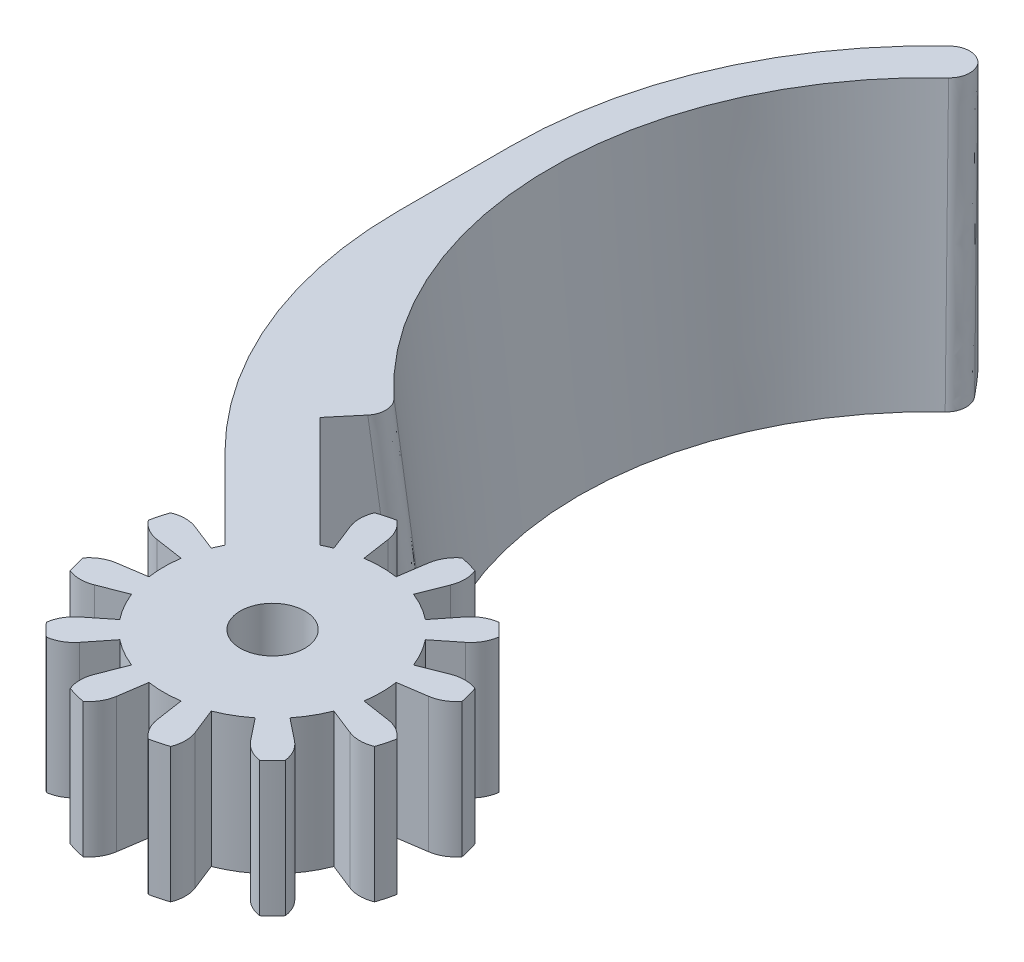
SolidWorks part; units mm, degrees
ref_plane "Plan de face" through (0, 0, 0) normal (0, 0, 1) x (1, 0, 0)
ref_plane "Plan de dessus" through (0, 0, 0) normal (0, 1, 0) x (1, 0, 0)
ref_plane "Plan de droite" through (0, 0, 0) normal (1, 0, 0) x (0, 0, -1)
sketch "Esquisse1" plane through (0, 0, 0) normal (0, 1, 0) x (1, 0, 0)
  line L0 (0, 0) -> (0, 27.3284) construction
  line L1 (-38.1202, 0) -> (19.7056, 0) construction
  line L2 (8.75, 40) -> (-53.1888, 40) construction
  line L3 (8.75, 40) -> (-13.9541, 12.9423) construction
  line L4 (8.75, 40) -> (-15.7208, 69.1632) construction
  line L5 (-22.25, 47.3971) -> (-22.25, -30.6529) construction
  line L6 (0, 0) -> (-33.9162, 33.9162) construction
  line L7 (-13.1703, 9.6348) -> (-7.1971, 3.6616)
  line L8 (-11.8794, 15.4149) -> (-3.6616, 7.1971)
  line L9 (-22.25, 40) -> (-22.25, 31.5551)
  line L10 (0, 0) -> (3.5575, 13.2769) construction
  line L11 (0, 0) -> (7.0447, 12.2018) construction
  line L12 (0, 0) -> (4.3209, 13.1034) construction
  line L13 (0, 0) -> (5.1162, 12.9881) construction
  line L14 (3.7383, 9.4903) -> (2.9595, 7.5131)
  line L15 (1.5077, 10.088) -> (1.1936, 7.9863)
  line L16 (6.3496, 7.9826) -> (5.0268, 6.3196)
  line L17 (7.9826, 6.3496) -> (6.3196, 5.0268)
  line L18 (9.4903, 3.7383) -> (7.5131, 2.9595)
  line L19 (10.088, 1.5077) -> (7.9863, 1.1936)
  line L20 (10.088, -1.5077) -> (7.9863, -1.1936)
  line L21 (9.4903, -3.7383) -> (7.5131, -2.9595)
  line L22 (7.9826, -6.3496) -> (6.3196, -5.0268)
  line L23 (6.3496, -7.9826) -> (5.0268, -6.3196)
  line L24 (3.7383, -9.4903) -> (2.9595, -7.5131)
  line L25 (1.5077, -10.088) -> (1.1936, -7.9863)
  line L26 (-1.5077, -10.088) -> (-1.1936, -7.9863)
  line L27 (-3.7383, -9.4903) -> (-2.9595, -7.5131)
  line L28 (-6.3496, -7.9826) -> (-5.0268, -6.3196)
  line L29 (-7.9826, -6.3496) -> (-6.3196, -5.0268)
  line L30 (-9.4903, -3.7383) -> (-7.5131, -2.9595)
  line L31 (-10.088, -1.5077) -> (-7.9863, -1.1936)
  line L32 (-10.088, 1.5077) -> (-7.9863, 1.1936)
  line L33 (-9.4903, 3.7383) -> (-7.5131, 2.9595)
  line L34 (-17.25, 40) -> (-17.25, -30.6529) construction
  line L36 (-3.7383, 9.4903) -> (-2.9595, 7.5131)
  line L37 (-1.5077, 10.088) -> (-1.1936, 7.9863)
  line L38 (-7.9826, 6.3496) -> (-6.3196, 5.0268) [skipped]
  line L39 (-6.3496, 7.9826) -> (-5.0268, 6.3196) [skipped]
  line L40 (-11.8794, 15.4149) -> (-7.9625, 20.0828)
  line L41 (-10.1877, 62.5691) -> (-7.9625, 59.9172)
  line L42 (8.75, 40) -> (8.75, 0) construction
  circle A0 centre (0, 0) radius 11.9 construction
  circle A1 centre (0, 0) radius 10.2 construction
  circle A2 centre (0, 0) radius 8.075 construction
  circle A3 centre (8.75, 40) radius 25 construction
  arc A4 (-7.9625, 59.9172) -> (-7.9625, 20.0828) centre (8.75, 40) ccw
  arc A5 (-22.25, 40) -> (-12.3581, 62.7035) centre (8.75, 40) cw
  arc A7 (3.7266, 11.3014) -> (3.7383, 9.4903) centre (1.4762, 10.3813) cw
  arc A8 (3.7266, 11.3014) -> (2.4233, 11.6506) centre (0, 0) ccw
  arc A9 (4.0375, 6.9932) -> (2.9595, 7.5131) centre (0, 0) ccw
  arc A10 (0, 8.075) -> (1.1936, 7.9863) centre (0, 0) cw
  arc A11 (2.4233, 11.6506) -> (1.5077, 10.088) centre (3.9122, 9.7286) ccw
  arc A12 (4.0375, 6.9932) -> (5.0268, 6.3196) centre (0, 0) cw
  arc A13 (7.924, 8.8781) -> (6.3496, 7.9826) centre (8.2524, 6.4691) ccw
  arc A14 (8.8781, 7.924) -> (7.924, 8.8781) centre (0, 0) ccw
  arc A15 (8.8781, 7.924) -> (7.9826, 6.3496) centre (6.4691, 8.2524) cw
  arc A16 (6.9932, 4.0375) -> (6.3196, 5.0268) centre (0, 0) ccw
  arc A17 (6.9932, 4.0375) -> (7.5131, 2.9595) centre (0, 0) cw
  arc A18 (11.3014, 3.7266) -> (9.4903, 3.7383) centre (10.3813, 1.4762) ccw
  arc A19 (11.6506, 2.4233) -> (11.3014, 3.7266) centre (0, 0) ccw
  arc A20 (11.6506, 2.4233) -> (10.088, 1.5077) centre (9.7286, 3.9122) cw
  arc A21 (8.075, 0) -> (7.9863, 1.1936) centre (0, 0) ccw
  arc A22 (8.075, 0) -> (7.9863, -1.1936) centre (0, 0) cw
  arc A23 (11.6506, -2.4233) -> (10.088, -1.5077) centre (9.7286, -3.9122) ccw
  arc A24 (11.3014, -3.7266) -> (11.6506, -2.4233) centre (0, 0) ccw
  arc A25 (11.3014, -3.7266) -> (9.4903, -3.7383) centre (10.3813, -1.4762) cw
  arc A26 (6.9932, -4.0375) -> (7.5131, -2.9595) centre (0, 0) ccw
  arc A27 (6.9932, -4.0375) -> (6.3196, -5.0268) centre (0, 0) cw
  arc A28 (8.8781, -7.924) -> (7.9826, -6.3496) centre (6.4691, -8.2524) ccw
  arc A29 (7.924, -8.8781) -> (8.8781, -7.924) centre (0, 0) ccw
  arc A30 (7.924, -8.8781) -> (6.3496, -7.9826) centre (8.2524, -6.4691) cw
  arc A31 (4.0375, -6.9932) -> (5.0268, -6.3196) centre (0, 0) ccw
  arc A32 (4.0375, -6.9932) -> (2.9595, -7.5131) centre (0, 0) cw
  arc A33 (3.7266, -11.3014) -> (3.7383, -9.4903) centre (1.4762, -10.3813) ccw
  arc A34 (2.4233, -11.6506) -> (3.7266, -11.3014) centre (0, 0) ccw
  arc A35 (2.4233, -11.6506) -> (1.5077, -10.088) centre (3.9122, -9.7286) cw
  arc A36 (0, -8.075) -> (1.1936, -7.9863) centre (0, 0) ccw
  arc A37 (0, -8.075) -> (-1.1936, -7.9863) centre (0, 0) cw
  arc A38 (-2.4233, -11.6506) -> (-1.5077, -10.088) centre (-3.9122, -9.7286) ccw
  arc A39 (-3.7266, -11.3014) -> (-2.4233, -11.6506) centre (0, 0) ccw
  arc A40 (-3.7266, -11.3014) -> (-3.7383, -9.4903) centre (-1.4762, -10.3813) cw
  arc A41 (-4.0375, -6.9932) -> (-2.9595, -7.5131) centre (0, 0) ccw
  arc A42 (-4.0375, -6.9932) -> (-5.0268, -6.3196) centre (0, 0) cw
  arc A43 (-7.924, -8.8781) -> (-6.3496, -7.9826) centre (-8.2524, -6.4691) ccw
  arc A44 (-8.8781, -7.924) -> (-7.924, -8.8781) centre (0, 0) ccw
  arc A45 (-8.8781, -7.924) -> (-7.9826, -6.3496) centre (-6.4691, -8.2524) cw
  arc A46 (-6.9932, -4.0375) -> (-6.3196, -5.0268) centre (0, 0) ccw
  arc A47 (-6.9932, -4.0375) -> (-7.5131, -2.9595) centre (0, 0) cw
  arc A48 (-11.3014, -3.7266) -> (-9.4903, -3.7383) centre (-10.3813, -1.4762) ccw
  arc A49 (-11.6506, -2.4233) -> (-11.3014, -3.7266) centre (0, 0) ccw
  arc A50 (-11.6506, -2.4233) -> (-10.088, -1.5077) centre (-9.7286, -3.9122) cw
  arc A51 (-8.075, 0) -> (-7.9863, -1.1936) centre (0, 0) ccw
  arc A52 (-8.075, 0) -> (-7.9863, 1.1936) centre (0, 0) cw
  arc A53 (-11.6506, 2.4233) -> (-10.088, 1.5077) centre (-9.7286, 3.9122) ccw
  arc A54 (-11.3014, 3.7266) -> (-11.6506, 2.4233) centre (0, 0) ccw
  arc A55 (-11.3014, 3.7266) -> (-9.4903, 3.7383) centre (-10.3813, 1.4762) cw
  arc A56 (-2.9595, 7.5131) -> (-3.6616, 7.1971) centre (0, 0) ccw
  arc A57 (-7.5131, 2.9595) -> (-7.1971, 3.6616) centre (0, 0) cw
  arc A60 (-13.1703, 9.6348) -> (-22.25, 31.5551) centre (8.75, 31.5551) cw
  arc A61 (-12.3581, 62.7035) -> (-10.1877, 62.5691) centre (-11.3368, 61.6049) cw
  arc A63 (-3.7266, 11.3014) -> (-3.7383, 9.4903) centre (-1.4762, 10.3813) ccw
  arc A64 (-2.4233, 11.6506) -> (-3.7266, 11.3014) centre (0, 0) ccw
  arc A65 (-2.4233, 11.6506) -> (-1.5077, 10.088) centre (-3.9122, 9.7286) cw
  arc A66 (0, 8.075) -> (-1.1936, 7.9863) centre (0, 0) ccw
  arc A67 (-8.8781, 7.924) -> (-7.9826, 6.3496) centre (-6.4691, 8.2524) ccw [skipped]
  arc A68 (-7.924, 8.8781) -> (-8.8781, 7.924) centre (0, 0) ccw [skipped]
  arc A69 (-7.924, 8.8781) -> (-6.3496, 7.9826) centre (-8.2524, 6.4691) cw [skipped]
  arc A70 (-6.9932, 4.0375) -> (-6.3196, 5.0268) centre (0, 0) cw [skipped]
  arc A71 (-4.0375, 6.9932) -> (-5.0268, 6.3196) centre (0, 0) ccw [skipped]
  arc A72 (-4.0375, 6.9932) -> (-2.9595, 7.5131) centre (0, 0) cw [skipped]
  arc A73 (-6.9932, 4.0375) -> (-7.5131, 2.9595) centre (0, 0) ccw [skipped]
  point P72 (0, 0)
  point P135 (-17.25, 20.2855)
  point P138 (-22.25, 18.7145)
  point P155 (-11.1764, 63.7474)
  point P169 (-10.855, 16.6356)
  point P176 (-17.25, 23.2668)
  dimension "D1" = 50
  dimension "D2" = 50
  dimension "D5" = 20.4
  dimension "D6" = 23.8
  dimension "D7" = 16.15
  dimension "D11" = 26
  dimension "D12" = 5
  dimension "D17" = 12
  dimension "D18" = 5
  dimension "D20" = 1.5
  dimension "D3" = 40
  dimension "D4" = 50
  dimension "D9" = 45
  dimension "D10" = 5
  dimension "D13" = 8.75
  dimension "D14" = 3.25
  dimension "D15" = 6.5
  dimension "D16" = 15
extrude "Boss.-Extru.1" add sketch "Esquisse1" along normal blind 10
sketch "Esquisse2" plane through (0, 0, 0) normal (0, -1, 0) x (1, 0, 0)
  line L0 (-11.8794, -15.4149) -> (-7.9625, -20.0828) construction
  line L30 (-2.9595, -7.5131) -> (-3.7383, -9.4903)
  line L31 (-1.5077, -10.088) -> (-1.1936, -7.9863)
  line L32 (1.1936, -7.9863) -> (1.5077, -10.088)
  line L33 (3.7383, -9.4903) -> (2.9595, -7.5131)
  line L34 (5.0268, -6.3196) -> (6.3496, -7.9826)
  line L35 (7.9826, -6.3496) -> (6.3196, -5.0268)
  line L36 (7.5131, -2.9595) -> (9.4903, -3.7383)
  line L37 (10.088, -1.5077) -> (7.9863, -1.1936)
  line L38 (7.9863, 1.1936) -> (10.088, 1.5077)
  line L39 (9.4903, 3.7383) -> (7.5131, 2.9595)
  line L40 (6.3196, 5.0268) -> (7.9826, 6.3496)
  line L41 (6.3496, 7.9826) -> (5.0268, 6.3196)
  line L42 (2.9595, 7.5131) -> (3.7383, 9.4903)
  line L43 (1.5077, 10.088) -> (1.1936, 7.9863)
  line L44 (-1.1936, 7.9863) -> (-1.5077, 10.088)
  line L45 (-3.7383, 9.4903) -> (-2.9595, 7.5131)
  line L46 (-5.0268, 6.3196) -> (-6.3496, 7.9826)
  line L47 (-7.9826, 6.3496) -> (-6.3196, 5.0268)
  line L48 (-7.5131, 2.9595) -> (-9.4903, 3.7383)
  line L49 (-10.088, 1.5077) -> (-7.9863, 1.1936)
  line L50 (-7.9863, -1.1936) -> (-10.088, -1.5077)
  line L51 (-9.4903, -3.7383) -> (-7.5131, -2.9595)
  line L52 (-7.1971, -3.6616) -> (-13.1703, -9.6348)
  line L54 (-11.8794, -15.4149) -> (-3.6616, -7.1971)
  line L55 (-11.8794, -15.4149) -> (-3.6616, -7.1971)
  line L58 (-2.9595, -7.5131) -> (-3.7383, -9.4903)
  line L59 (-1.5077, -10.088) -> (-1.1936, -7.9863)
  line L60 (1.1936, -7.9863) -> (1.5077, -10.088)
  line L61 (3.7383, -9.4903) -> (2.9595, -7.5131)
  line L62 (5.0268, -6.3196) -> (6.3496, -7.9826)
  line L63 (7.9826, -6.3496) -> (6.3196, -5.0268)
  line L64 (7.5131, -2.9595) -> (9.4903, -3.7383)
  line L65 (10.088, -1.5077) -> (7.9863, -1.1936)
  line L66 (7.9863, 1.1936) -> (10.088, 1.5077)
  line L67 (9.4903, 3.7383) -> (7.5131, 2.9595)
  line L68 (6.3196, 5.0268) -> (7.9826, 6.3496)
  line L69 (6.3496, 7.9826) -> (5.0268, 6.3196)
  line L70 (2.9595, 7.5131) -> (3.7383, 9.4903)
  line L71 (1.5077, 10.088) -> (1.1936, 7.9863)
  line L72 (-1.1936, 7.9863) -> (-1.5077, 10.088)
  line L73 (-3.7383, 9.4903) -> (-2.9595, 7.5131)
  line L74 (-5.0268, 6.3196) -> (-6.3496, 7.9826)
  line L75 (-7.9826, 6.3496) -> (-6.3196, 5.0268)
  line L76 (-7.5131, 2.9595) -> (-9.4903, 3.7383)
  line L77 (-10.088, 1.5077) -> (-7.9863, 1.1936)
  line L78 (-7.9863, -1.1936) -> (-10.088, -1.5077)
  line L79 (-9.4903, -3.7383) -> (-7.5131, -2.9595)
  line L80 (-7.1971, -3.6616) -> (-13.1703, -9.6348)
  line L84 (-22.25, -31.5551) -> (-22.25, -40)
  line L85 (-22.25, -31.5551) -> (-22.25, -40)
  line L86 (-10.1877, -62.5691) -> (-7.9625, -59.9172)
  line L87 (-10.1877, -62.5691) -> (-7.9625, -59.9172)
  line L88 (-7.9625, -20.0828) -> (-11.8794, -15.4149)
  line L89 (-7.9625, -20.0828) -> (-11.8794, -15.4149)
  arc A0 (-11.1764, -16.2526) -> (-15.2252, -59.6518) centre (8.75, -40) ccw
  arc A56 (-3.7383, -9.4903) -> (-3.7266, -11.3014) centre (-1.4762, -10.3813) ccw
  arc A57 (-3.7266, -11.3014) -> (-2.4233, -11.6506) centre (0, 0) ccw
  arc A58 (-2.4233, -11.6506) -> (-1.5077, -10.088) centre (-3.9122, -9.7286) ccw
  arc A59 (-1.1936, -7.9863) -> (1.1936, -7.9863) centre (0, 0) ccw
  arc A60 (1.5077, -10.088) -> (2.4233, -11.6506) centre (3.9122, -9.7286) ccw
  arc A61 (2.4233, -11.6506) -> (3.7266, -11.3014) centre (0, 0) ccw
  arc A62 (3.7266, -11.3014) -> (3.7383, -9.4903) centre (1.4762, -10.3813) ccw
  arc A63 (2.9595, -7.5131) -> (5.0268, -6.3196) centre (0, 0) ccw
  arc A64 (6.3496, -7.9826) -> (7.924, -8.8781) centre (8.2524, -6.4691) ccw
  arc A65 (7.924, -8.8781) -> (8.8781, -7.924) centre (0, 0) ccw
  arc A66 (8.8781, -7.924) -> (7.9826, -6.3496) centre (6.4691, -8.2524) ccw
  arc A67 (6.3196, -5.0268) -> (7.5131, -2.9595) centre (0, 0) ccw
  arc A68 (9.4903, -3.7383) -> (11.3014, -3.7266) centre (10.3813, -1.4762) ccw
  arc A69 (11.3014, -3.7266) -> (11.6506, -2.4233) centre (0, 0) ccw
  arc A70 (11.6506, -2.4233) -> (10.088, -1.5077) centre (9.7286, -3.9122) ccw
  arc A71 (7.9863, -1.1936) -> (7.9863, 1.1936) centre (0, 0) ccw
  arc A72 (10.088, 1.5077) -> (11.6506, 2.4233) centre (9.7286, 3.9122) ccw
  arc A73 (11.6506, 2.4233) -> (11.3014, 3.7266) centre (0, 0) ccw
  arc A74 (11.3014, 3.7266) -> (9.4903, 3.7383) centre (10.3813, 1.4762) ccw
  arc A75 (7.5131, 2.9595) -> (6.3196, 5.0268) centre (0, 0) ccw
  arc A76 (7.9826, 6.3496) -> (8.8781, 7.924) centre (6.4691, 8.2524) ccw
  arc A77 (8.8781, 7.924) -> (7.924, 8.8781) centre (0, 0) ccw
  arc A78 (7.924, 8.8781) -> (6.3496, 7.9826) centre (8.2524, 6.4691) ccw
  arc A79 (5.0268, 6.3196) -> (2.9595, 7.5131) centre (0, 0) ccw
  arc A80 (3.7383, 9.4903) -> (3.7266, 11.3014) centre (1.4762, 10.3813) ccw
  arc A81 (3.7266, 11.3014) -> (2.4233, 11.6506) centre (0, 0) ccw
  arc A82 (2.4233, 11.6506) -> (1.5077, 10.088) centre (3.9122, 9.7286) ccw
  arc A83 (1.1936, 7.9863) -> (-1.1936, 7.9863) centre (0, 0) ccw
  arc A84 (-1.5077, 10.088) -> (-2.4233, 11.6506) centre (-3.9122, 9.7286) ccw
  arc A85 (-2.4233, 11.6506) -> (-3.7266, 11.3014) centre (0, 0) ccw
  arc A86 (-3.7266, 11.3014) -> (-3.7383, 9.4903) centre (-1.4762, 10.3813) ccw
  arc A87 (-2.9595, 7.5131) -> (-5.0268, 6.3196) centre (0, 0) ccw
  arc A88 (-6.3496, 7.9826) -> (-7.924, 8.8781) centre (-8.2524, 6.4691) ccw
  arc A89 (-7.924, 8.8781) -> (-8.8781, 7.924) centre (0, 0) ccw
  arc A90 (-8.8781, 7.924) -> (-7.9826, 6.3496) centre (-6.4691, 8.2524) ccw
  arc A91 (-6.3196, 5.0268) -> (-7.5131, 2.9595) centre (0, 0) ccw
  arc A92 (-9.4903, 3.7383) -> (-11.3014, 3.7266) centre (-10.3813, 1.4762) ccw
  arc A93 (-11.3014, 3.7266) -> (-11.6506, 2.4233) centre (0, 0) ccw
  arc A94 (-11.6506, 2.4233) -> (-10.088, 1.5077) centre (-9.7286, 3.9122) ccw
  arc A95 (-7.9863, 1.1936) -> (-7.9863, -1.1936) centre (0, 0) ccw
  arc A96 (-10.088, -1.5077) -> (-11.6506, -2.4233) centre (-9.7286, -3.9122) ccw
  arc A97 (-11.6506, -2.4233) -> (-11.3014, -3.7266) centre (0, 0) ccw
  arc A98 (-11.3014, -3.7266) -> (-9.4903, -3.7383) centre (-10.3813, -1.4762) ccw
  arc A99 (-7.5131, -2.9595) -> (-7.1971, -3.6616) centre (0, 0) ccw
  arc A102 (-3.6616, -7.1971) -> (-2.9595, -7.5131) centre (0, 0) ccw
  arc A103 (-3.6616, -7.1971) -> (-2.9595, -7.5131) centre (0, 0) ccw
  arc A104 (-13.1703, -9.6348) -> (-22.25, -31.5551) centre (8.75, -31.5551) ccw
  arc A105 (-13.1703, -9.6348) -> (-22.25, -31.5551) centre (8.75, -31.5551) ccw
  arc A109 (-3.7383, -9.4903) -> (-3.7266, -11.3014) centre (-1.4762, -10.3813) ccw
  arc A110 (-3.7266, -11.3014) -> (-2.4233, -11.6506) centre (0, 0) ccw
  arc A111 (-2.4233, -11.6506) -> (-1.5077, -10.088) centre (-3.9122, -9.7286) ccw
  arc A112 (-1.1936, -7.9863) -> (1.1936, -7.9863) centre (0, 0) ccw
  arc A113 (1.5077, -10.088) -> (2.4233, -11.6506) centre (3.9122, -9.7286) ccw
  arc A114 (2.4233, -11.6506) -> (3.7266, -11.3014) centre (0, 0) ccw
  arc A115 (3.7266, -11.3014) -> (3.7383, -9.4903) centre (1.4762, -10.3813) ccw
  arc A116 (2.9595, -7.5131) -> (5.0268, -6.3196) centre (0, 0) ccw
  arc A117 (6.3496, -7.9826) -> (7.924, -8.8781) centre (8.2524, -6.4691) ccw
  arc A118 (7.924, -8.8781) -> (8.8781, -7.924) centre (0, 0) ccw
  arc A119 (8.8781, -7.924) -> (7.9826, -6.3496) centre (6.4691, -8.2524) ccw
  arc A120 (6.3196, -5.0268) -> (7.5131, -2.9595) centre (0, 0) ccw
  arc A121 (9.4903, -3.7383) -> (11.3014, -3.7266) centre (10.3813, -1.4762) ccw
  arc A122 (11.3014, -3.7266) -> (11.6506, -2.4233) centre (0, 0) ccw
  arc A123 (11.6506, -2.4233) -> (10.088, -1.5077) centre (9.7286, -3.9122) ccw
  arc A124 (7.9863, -1.1936) -> (7.9863, 1.1936) centre (0, 0) ccw
  arc A125 (10.088, 1.5077) -> (11.6506, 2.4233) centre (9.7286, 3.9122) ccw
  arc A126 (11.6506, 2.4233) -> (11.3014, 3.7266) centre (0, 0) ccw
  arc A127 (11.3014, 3.7266) -> (9.4903, 3.7383) centre (10.3813, 1.4762) ccw
  arc A128 (7.5131, 2.9595) -> (6.3196, 5.0268) centre (0, 0) ccw
  arc A129 (7.9826, 6.3496) -> (8.8781, 7.924) centre (6.4691, 8.2524) ccw
  arc A130 (8.8781, 7.924) -> (7.924, 8.8781) centre (0, 0) ccw
  arc A131 (7.924, 8.8781) -> (6.3496, 7.9826) centre (8.2524, 6.4691) ccw
  arc A132 (5.0268, 6.3196) -> (2.9595, 7.5131) centre (0, 0) ccw
  arc A133 (3.7383, 9.4903) -> (3.7266, 11.3014) centre (1.4762, 10.3813) ccw
  arc A134 (3.7266, 11.3014) -> (2.4233, 11.6506) centre (0, 0) ccw
  arc A135 (2.4233, 11.6506) -> (1.5077, 10.088) centre (3.9122, 9.7286) ccw
  arc A136 (1.1936, 7.9863) -> (-1.1936, 7.9863) centre (0, 0) ccw
  arc A137 (-1.5077, 10.088) -> (-2.4233, 11.6506) centre (-3.9122, 9.7286) ccw
  arc A138 (-2.4233, 11.6506) -> (-3.7266, 11.3014) centre (0, 0) ccw
  arc A139 (-3.7266, 11.3014) -> (-3.7383, 9.4903) centre (-1.4762, 10.3813) ccw
  arc A140 (-2.9595, 7.5131) -> (-5.0268, 6.3196) centre (0, 0) ccw
  arc A141 (-6.3496, 7.9826) -> (-7.924, 8.8781) centre (-8.2524, 6.4691) ccw
  arc A142 (-7.924, 8.8781) -> (-8.8781, 7.924) centre (0, 0) ccw
  arc A143 (-8.8781, 7.924) -> (-7.9826, 6.3496) centre (-6.4691, 8.2524) ccw
  arc A144 (-6.3196, 5.0268) -> (-7.5131, 2.9595) centre (0, 0) ccw
  arc A145 (-9.4903, 3.7383) -> (-11.3014, 3.7266) centre (-10.3813, 1.4762) ccw
  arc A146 (-11.3014, 3.7266) -> (-11.6506, 2.4233) centre (0, 0) ccw
  arc A147 (-11.6506, 2.4233) -> (-10.088, 1.5077) centre (-9.7286, 3.9122) ccw
  arc A148 (-7.9863, 1.1936) -> (-7.9863, -1.1936) centre (0, 0) ccw
  arc A149 (-10.088, -1.5077) -> (-11.6506, -2.4233) centre (-9.7286, -3.9122) ccw
  arc A150 (-11.6506, -2.4233) -> (-11.3014, -3.7266) centre (0, 0) ccw
  arc A151 (-11.3014, -3.7266) -> (-9.4903, -3.7383) centre (-10.3813, -1.4762) ccw
  arc A152 (-7.5131, -2.9595) -> (-7.1971, -3.6616) centre (0, 0) ccw
  arc A159 (-22.25, -40) -> (-12.3581, -62.7035) centre (8.75, -40) ccw
  arc A160 (-22.25, -40) -> (-12.3581, -62.7035) centre (8.75, -40) ccw
  arc A161 (-12.3581, -62.7035) -> (-10.1877, -62.5691) centre (-11.3368, -61.6049) ccw
  arc A162 (-12.3581, -62.7035) -> (-10.1877, -62.5691) centre (-11.3368, -61.6049) ccw
  arc A163 (-7.9625, -20.0828) -> (-7.9625, -59.9172) centre (8.75, -40) ccw
  arc A164 (-7.9625, -20.0828) -> (-7.9625, -59.9172) centre (8.75, -40) ccw
  dimension "D1" = 0
extrude "Boss.-Extru.2" add sketch "Esquisse2" along normal blind 10
chamfer "Chanfrein1" distance 20 angle 6.03 1 edges at (-17.25, 10, -40)
fillet "Congé1" radius 1.5 2 edges at (-8.6415, 0, -60.7264) (-8.6415, 0, -19.2736)
chamfer "Chanfrein2" distance 10 angle 6.03 1 edges at (-22.24, -10, -39.2116)
fillet "Congé2" radius 1.5 1 edges at (-21.1936, -10, -39.9603)
sketch "Esquisse3" plane through (0, 10, 0) normal (0, 1, 0) x (1, 0, 0)
  line L26 (-22.25, 40) -> (-22.25, 31.5551)
  line L27 (-13.1703, 9.6348) -> (-7.1971, 3.6616)
  line L28 (-7.5131, 2.9595) -> (-9.4903, 3.7383)
  line L29 (-10.088, 1.5077) -> (-7.9863, 1.1936)
  line L30 (-7.9863, -1.1936) -> (-10.088, -1.5077)
  line L31 (-9.4903, -3.7383) -> (-7.5131, -2.9595)
  line L32 (-6.3196, -5.0268) -> (-7.9826, -6.3496)
  line L33 (-6.3496, -7.9826) -> (-5.0268, -6.3196)
  line L34 (-2.9595, -7.5131) -> (-3.7383, -9.4903)
  line L35 (-1.5077, -10.088) -> (-1.1936, -7.9863)
  line L36 (1.1936, -7.9863) -> (1.5077, -10.088)
  line L37 (3.7383, -9.4903) -> (2.9595, -7.5131)
  line L38 (5.0268, -6.3196) -> (6.3496, -7.9826)
  line L39 (7.9826, -6.3496) -> (6.3196, -5.0268)
  line L40 (7.5131, -2.9595) -> (9.4903, -3.7383)
  line L41 (10.088, -1.5077) -> (7.9863, -1.1936)
  line L42 (7.9863, 1.1936) -> (10.088, 1.5077)
  line L43 (9.4903, 3.7383) -> (7.5131, 2.9595)
  line L44 (6.3196, 5.0268) -> (7.9826, 6.3496)
  line L45 (6.3496, 7.9826) -> (5.0268, 6.3196)
  line L46 (2.9595, 7.5131) -> (3.7383, 9.4903)
  line L47 (1.5077, 10.088) -> (1.1936, 7.9863)
  line L48 (-1.1936, 7.9863) -> (-1.5077, 10.088)
  line L49 (-3.7383, 9.4903) -> (-2.9595, 7.5131)
  line L50 (-3.6616, 7.1971) -> (-11.8794, 15.4149)
  line L51 (-11.8794, 15.4149) -> (-10.2656, 17.3381)
  line L52 (-22.25, 40) -> (-22.25, 31.5551)
  line L53 (-13.1703, 9.6348) -> (-7.1971, 3.6616)
  line L54 (-7.5131, 2.9595) -> (-9.4903, 3.7383)
  line L55 (-10.088, 1.5077) -> (-7.9863, 1.1936)
  line L56 (-7.9863, -1.1936) -> (-10.088, -1.5077)
  line L57 (-9.4903, -3.7383) -> (-7.5131, -2.9595)
  line L58 (-6.3196, -5.0268) -> (-7.9826, -6.3496)
  line L59 (-6.3496, -7.9826) -> (-5.0268, -6.3196)
  line L60 (-2.9595, -7.5131) -> (-3.7383, -9.4903)
  line L61 (-1.5077, -10.088) -> (-1.1936, -7.9863)
  line L62 (1.1936, -7.9863) -> (1.5077, -10.088)
  line L63 (3.7383, -9.4903) -> (2.9595, -7.5131)
  line L64 (5.0268, -6.3196) -> (6.3496, -7.9826)
  line L65 (7.9826, -6.3496) -> (6.3196, -5.0268)
  line L66 (7.5131, -2.9595) -> (9.4903, -3.7383)
  line L67 (10.088, -1.5077) -> (7.9863, -1.1936)
  line L68 (7.9863, 1.1936) -> (10.088, 1.5077)
  line L69 (9.4903, 3.7383) -> (7.5131, 2.9595)
  line L70 (6.3196, 5.0268) -> (7.9826, 6.3496)
  line L71 (6.3496, 7.9826) -> (5.0268, 6.3196)
  line L72 (2.9595, 7.5131) -> (3.7383, 9.4903)
  line L73 (1.5077, 10.088) -> (1.1936, 7.9863)
  line L74 (-1.1936, 7.9863) -> (-1.5077, 10.088)
  line L75 (-3.7383, 9.4903) -> (-2.9595, 7.5131)
  line L76 (-3.6616, 7.1971) -> (-11.8794, 15.4149)
  line L77 (-11.8794, 15.4149) -> (-10.2656, 17.3381)
  circle A0 centre (0, 0) radius 2.4
  arc A49 (-10.3884, 60.5923) -> (-10.3884, 19.4077) centre (8.75, 40) ccw
  arc A50 (-10.2275, 62.6146) -> (-12.3581, 62.7035) centre (-11.3368, 61.6049) ccw
  arc A51 (-12.3581, 62.7035) -> (-22.25, 40) centre (8.75, 40) ccw
  arc A52 (-22.25, 31.5551) -> (-13.1703, 9.6348) centre (8.75, 31.5551) ccw
  arc A53 (-7.1971, 3.6616) -> (-7.5131, 2.9595) centre (0, 0) ccw
  arc A54 (-9.4903, 3.7383) -> (-11.3014, 3.7266) centre (-10.3813, 1.4762) ccw
  arc A55 (-11.3014, 3.7266) -> (-11.6506, 2.4233) centre (0, 0) ccw
  arc A56 (-11.6506, 2.4233) -> (-10.088, 1.5077) centre (-9.7286, 3.9122) ccw
  arc A57 (-7.9863, 1.1936) -> (-7.9863, -1.1936) centre (0, 0) ccw
  arc A58 (-10.088, -1.5077) -> (-11.6506, -2.4233) centre (-9.7286, -3.9122) ccw
  arc A59 (-11.6506, -2.4233) -> (-11.3014, -3.7266) centre (0, 0) ccw
  arc A60 (-11.3014, -3.7266) -> (-9.4903, -3.7383) centre (-10.3813, -1.4762) ccw
  arc A61 (-7.5131, -2.9595) -> (-6.3196, -5.0268) centre (0, 0) ccw
  arc A62 (-7.9826, -6.3496) -> (-8.8781, -7.924) centre (-6.4691, -8.2524) ccw
  arc A63 (-8.8781, -7.924) -> (-7.924, -8.8781) centre (0, 0) ccw
  arc A64 (-7.924, -8.8781) -> (-6.3496, -7.9826) centre (-8.2524, -6.4691) ccw
  arc A65 (-5.0268, -6.3196) -> (-2.9595, -7.5131) centre (0, 0) ccw
  arc A66 (-3.7383, -9.4903) -> (-3.7266, -11.3014) centre (-1.4762, -10.3813) ccw
  arc A67 (-3.7266, -11.3014) -> (-2.4233, -11.6506) centre (0, 0) ccw
  arc A68 (-2.4233, -11.6506) -> (-1.5077, -10.088) centre (-3.9122, -9.7286) ccw
  arc A69 (-1.1936, -7.9863) -> (1.1936, -7.9863) centre (0, 0) ccw
  arc A70 (1.5077, -10.088) -> (2.4233, -11.6506) centre (3.9122, -9.7286) ccw
  arc A71 (2.4233, -11.6506) -> (3.7266, -11.3014) centre (0, 0) ccw
  arc A72 (3.7266, -11.3014) -> (3.7383, -9.4903) centre (1.4762, -10.3813) ccw
  arc A73 (2.9595, -7.5131) -> (5.0268, -6.3196) centre (0, 0) ccw
  arc A74 (6.3496, -7.9826) -> (7.924, -8.8781) centre (8.2524, -6.4691) ccw
  arc A75 (7.924, -8.8781) -> (8.8781, -7.924) centre (0, 0) ccw
  arc A76 (8.8781, -7.924) -> (7.9826, -6.3496) centre (6.4691, -8.2524) ccw
  arc A77 (6.3196, -5.0268) -> (7.5131, -2.9595) centre (0, 0) ccw
  arc A78 (9.4903, -3.7383) -> (11.3014, -3.7266) centre (10.3813, -1.4762) ccw
  arc A79 (11.3014, -3.7266) -> (11.6506, -2.4233) centre (0, 0) ccw
  arc A80 (11.6506, -2.4233) -> (10.088, -1.5077) centre (9.7286, -3.9122) ccw
  arc A81 (7.9863, -1.1936) -> (7.9863, 1.1936) centre (0, 0) ccw
  arc A82 (10.088, 1.5077) -> (11.6506, 2.4233) centre (9.7286, 3.9122) ccw
  arc A83 (11.6506, 2.4233) -> (11.3014, 3.7266) centre (0, 0) ccw
  arc A84 (11.3014, 3.7266) -> (9.4903, 3.7383) centre (10.3813, 1.4762) ccw
  arc A85 (7.5131, 2.9595) -> (6.3196, 5.0268) centre (0, 0) ccw
  arc A86 (7.9826, 6.3496) -> (8.8781, 7.924) centre (6.4691, 8.2524) ccw
  arc A87 (8.8781, 7.924) -> (7.924, 8.8781) centre (0, 0) ccw
  arc A88 (7.924, 8.8781) -> (6.3496, 7.9826) centre (8.2524, 6.4691) ccw
  arc A89 (5.0268, 6.3196) -> (2.9595, 7.5131) centre (0, 0) ccw
  arc A90 (3.7383, 9.4903) -> (3.7266, 11.3014) centre (1.4762, 10.3813) ccw
  arc A91 (3.7266, 11.3014) -> (2.4233, 11.6506) centre (0, 0) ccw
  arc A92 (2.4233, 11.6506) -> (1.5077, 10.088) centre (3.9122, 9.7286) ccw
  arc A93 (1.1936, 7.9863) -> (-1.1936, 7.9863) centre (0, 0) ccw
  arc A94 (-1.5077, 10.088) -> (-2.4233, 11.6506) centre (-3.9122, 9.7286) ccw
  arc A95 (-2.4233, 11.6506) -> (-3.7266, 11.3014) centre (0, 0) ccw
  arc A96 (-3.7266, 11.3014) -> (-3.7383, 9.4903) centre (-1.4762, 10.3813) ccw
  arc A97 (-2.9595, 7.5131) -> (-3.6616, 7.1971) centre (0, 0) ccw
  arc A98 (-10.3884, 60.5923) -> (-10.3884, 19.4077) centre (8.75, 40) ccw
  arc A99 (-10.2275, 62.6146) -> (-12.3581, 62.7035) centre (-11.3368, 61.6049) ccw
  arc A100 (-12.3581, 62.7035) -> (-22.25, 40) centre (8.75, 40) ccw
  arc A101 (-22.25, 31.5551) -> (-13.1703, 9.6348) centre (8.75, 31.5551) ccw
  arc A102 (-7.1971, 3.6616) -> (-7.5131, 2.9595) centre (0, 0) ccw
  arc A103 (-9.4903, 3.7383) -> (-11.3014, 3.7266) centre (-10.3813, 1.4762) ccw
  arc A104 (-11.3014, 3.7266) -> (-11.6506, 2.4233) centre (0, 0) ccw
  arc A105 (-11.6506, 2.4233) -> (-10.088, 1.5077) centre (-9.7286, 3.9122) ccw
  arc A106 (-7.9863, 1.1936) -> (-7.9863, -1.1936) centre (0, 0) ccw
  arc A107 (-10.088, -1.5077) -> (-11.6506, -2.4233) centre (-9.7286, -3.9122) ccw
  arc A108 (-11.6506, -2.4233) -> (-11.3014, -3.7266) centre (0, 0) ccw
  arc A109 (-11.3014, -3.7266) -> (-9.4903, -3.7383) centre (-10.3813, -1.4762) ccw
  arc A110 (-7.5131, -2.9595) -> (-6.3196, -5.0268) centre (0, 0) ccw
  arc A111 (-7.9826, -6.3496) -> (-8.8781, -7.924) centre (-6.4691, -8.2524) ccw
  arc A112 (-8.8781, -7.924) -> (-7.924, -8.8781) centre (0, 0) ccw
  arc A113 (-7.924, -8.8781) -> (-6.3496, -7.9826) centre (-8.2524, -6.4691) ccw
  arc A114 (-5.0268, -6.3196) -> (-2.9595, -7.5131) centre (0, 0) ccw
  arc A115 (-3.7383, -9.4903) -> (-3.7266, -11.3014) centre (-1.4762, -10.3813) ccw
  arc A116 (-3.7266, -11.3014) -> (-2.4233, -11.6506) centre (0, 0) ccw
  arc A117 (-2.4233, -11.6506) -> (-1.5077, -10.088) centre (-3.9122, -9.7286) ccw
  arc A118 (-1.1936, -7.9863) -> (1.1936, -7.9863) centre (0, 0) ccw
  arc A119 (1.5077, -10.088) -> (2.4233, -11.6506) centre (3.9122, -9.7286) ccw
  arc A120 (2.4233, -11.6506) -> (3.7266, -11.3014) centre (0, 0) ccw
  arc A121 (3.7266, -11.3014) -> (3.7383, -9.4903) centre (1.4762, -10.3813) ccw
  arc A122 (2.9595, -7.5131) -> (5.0268, -6.3196) centre (0, 0) ccw
  arc A123 (6.3496, -7.9826) -> (7.924, -8.8781) centre (8.2524, -6.4691) ccw
  arc A124 (7.924, -8.8781) -> (8.8781, -7.924) centre (0, 0) ccw
  arc A125 (8.8781, -7.924) -> (7.9826, -6.3496) centre (6.4691, -8.2524) ccw
  arc A126 (6.3196, -5.0268) -> (7.5131, -2.9595) centre (0, 0) ccw
  arc A127 (9.4903, -3.7383) -> (11.3014, -3.7266) centre (10.3813, -1.4762) ccw
  arc A128 (11.3014, -3.7266) -> (11.6506, -2.4233) centre (0, 0) ccw
  arc A129 (11.6506, -2.4233) -> (10.088, -1.5077) centre (9.7286, -3.9122) ccw
  arc A130 (7.9863, -1.1936) -> (7.9863, 1.1936) centre (0, 0) ccw
  arc A131 (10.088, 1.5077) -> (11.6506, 2.4233) centre (9.7286, 3.9122) ccw
  arc A132 (11.6506, 2.4233) -> (11.3014, 3.7266) centre (0, 0) ccw
  arc A133 (11.3014, 3.7266) -> (9.4903, 3.7383) centre (10.3813, 1.4762) ccw
  arc A134 (7.5131, 2.9595) -> (6.3196, 5.0268) centre (0, 0) ccw
  arc A135 (7.9826, 6.3496) -> (8.8781, 7.924) centre (6.4691, 8.2524) ccw
  arc A136 (8.8781, 7.924) -> (7.924, 8.8781) centre (0, 0) ccw
  arc A137 (7.924, 8.8781) -> (6.3496, 7.9826) centre (8.2524, 6.4691) ccw
  arc A138 (5.0268, 6.3196) -> (2.9595, 7.5131) centre (0, 0) ccw
  arc A139 (3.7383, 9.4903) -> (3.7266, 11.3014) centre (1.4762, 10.3813) ccw
  arc A140 (3.7266, 11.3014) -> (2.4233, 11.6506) centre (0, 0) ccw
  arc A141 (2.4233, 11.6506) -> (1.5077, 10.088) centre (3.9122, 9.7286) ccw
  arc A142 (1.1936, 7.9863) -> (-1.1936, 7.9863) centre (0, 0) ccw
  arc A143 (-1.5077, 10.088) -> (-2.4233, 11.6506) centre (-3.9122, 9.7286) ccw
  arc A144 (-2.4233, 11.6506) -> (-3.7266, 11.3014) centre (0, 0) ccw
  arc A145 (-3.7266, 11.3014) -> (-3.7383, 9.4903) centre (-1.4762, 10.3813) ccw
  arc A146 (-2.9595, 7.5131) -> (-3.6616, 7.1971) centre (0, 0) ccw
  spline S2 degree 3 poles (539.9464, 1979.1164) (-162.3304, 121.4726) (-15.6404, 49.464) (-10.0195, 61.1214) (-9.9874, 61.208) (-9.9391, 61.3864) (-9.9231, 61.4792) (-9.0895, 72.0919) (-122.2782, 88.5994) (196.0199, -1924.92) knots -17.002933 -17.002933 -17.002933 -17.002933 0.25 0.25 0.375 0.375 0.5 0.5 14.727294 14.727294 14.727294 14.727294 only from (-10.3884, 60.5923) to (-10.2275, 62.6146)
  spline S3 degree 3 poles (373.4781, 1976.3154) (-161.9201, 54.2879) (-13.9646, 5.8717) (-9.9582, 17.9249) (-9.9369, 18.0173) (-9.9119, 18.2055) (-9.9082, 18.3023) (-9.9192, 18.4923) (-9.9335, 18.5859) (-9.9802, 18.7706) (-10.0127, 18.8618) (-14.326, 28.0625) (-112.9384, -3.6671) (698.2683, -1849.0244) knots -16.239807 -16.239807 -16.239807 -16.239807 0.25 0.25 0.375 0.375 0.5 0.5 0.625 0.625 0.75 0.75 14.012928 14.012928 14.012928 14.012928 only from (-10.2656, 17.3381) to (-10.3884, 19.4077)
  spline S4 degree 3 poles (-10.3884, 60.5923) (-10.2513, 60.7197) (-10.1408, 60.8699) (-10.0195, 61.1214) (-9.9874, 61.208) (-9.9391, 61.3864) (-9.9231, 61.4792) (-9.8868, 61.9413) (-9.9986, 62.3184) (-10.2275, 62.6146) knots 0 0 0 0 0.25 0.25 0.375 0.375 0.5 0.5 1 1 1 1
  spline S5 degree 3 poles (-10.2656, 17.3381) (-10.142, 17.4854) (-10.0486, 17.6529) (-9.9582, 17.9249) (-9.9369, 18.0173) (-9.9119, 18.2055) (-9.9082, 18.3023) (-9.9192, 18.4923) (-9.9335, 18.5859) (-9.9802, 18.7706) (-10.0127, 18.8618) (-10.1335, 19.1195) (-10.2476, 19.2768) (-10.3884, 19.4077) knots 0 0 0 0 0.25 0.25 0.375 0.375 0.5 0.5 0.625 0.625 0.75 0.75 1 1 1 1
  dimension "D2" = 4.8
  dimension "D1" = 0
extrude "Enlèv. mat.-Extru.1" cut sketch "Esquisse3" against normal blind 4 contours A0
sketch "Esquisse4" plane through (0, 0, 0) normal (0, -1, 0) x (1, 0, 0)
  line L26 (-11.1764, -16.2526) -> (-11.8794, -15.4149)
  line L27 (-11.8794, -15.4149) -> (-3.6616, -7.1971)
  line L28 (-2.9595, -7.5131) -> (-3.7383, -9.4903)
  line L29 (-1.5077, -10.088) -> (-1.1936, -7.9863)
  line L30 (1.1936, -7.9863) -> (1.5077, -10.088)
  line L31 (3.7383, -9.4903) -> (2.9595, -7.5131)
  line L32 (5.0268, -6.3196) -> (6.3496, -7.9826)
  line L33 (7.9826, -6.3496) -> (6.3196, -5.0268)
  line L34 (7.5131, -2.9595) -> (9.4903, -3.7383)
  line L35 (10.088, -1.5077) -> (7.9863, -1.1936)
  line L36 (7.9863, 1.1936) -> (10.088, 1.5077)
  line L37 (9.4903, 3.7383) -> (7.5131, 2.9595)
  line L38 (6.3196, 5.0268) -> (7.9826, 6.3496)
  line L39 (6.3496, 7.9826) -> (5.0268, 6.3196)
  line L40 (2.9595, 7.5131) -> (3.7383, 9.4903)
  line L41 (1.5077, 10.088) -> (1.1936, 7.9863)
  line L42 (-1.1936, 7.9863) -> (-1.5077, 10.088)
  line L43 (-3.7383, 9.4903) -> (-2.9595, 7.5131)
  line L44 (-5.0268, 6.3196) -> (-6.3496, 7.9826)
  line L45 (-7.9826, 6.3496) -> (-6.3196, 5.0268)
  line L46 (-7.5131, 2.9595) -> (-9.4903, 3.7383)
  line L47 (-10.088, 1.5077) -> (-7.9863, 1.1936)
  line L48 (-7.9863, -1.1936) -> (-10.088, -1.5077)
  line L49 (-9.4903, -3.7383) -> (-7.5131, -2.9595)
  line L50 (-7.1971, -3.6616) -> (-13.1703, -9.6348)
  line L51 (-22.25, -31.5551) -> (-22.25, -40)
  line L52 (-11.1764, -16.2526) -> (-11.8794, -15.4149)
  line L53 (-11.8794, -15.4149) -> (-3.6616, -7.1971)
  line L54 (-2.9595, -7.5131) -> (-3.7383, -9.4903)
  line L55 (-1.5077, -10.088) -> (-1.1936, -7.9863)
  line L56 (1.1936, -7.9863) -> (1.5077, -10.088)
  line L57 (3.7383, -9.4903) -> (2.9595, -7.5131)
  line L58 (5.0268, -6.3196) -> (6.3496, -7.9826)
  line L59 (7.9826, -6.3496) -> (6.3196, -5.0268)
  line L60 (7.5131, -2.9595) -> (9.4903, -3.7383)
  line L61 (10.088, -1.5077) -> (7.9863, -1.1936)
  line L62 (7.9863, 1.1936) -> (10.088, 1.5077)
  line L63 (9.4903, 3.7383) -> (7.5131, 2.9595)
  line L64 (6.3196, 5.0268) -> (7.9826, 6.3496)
  line L65 (6.3496, 7.9826) -> (5.0268, 6.3196)
  line L66 (2.9595, 7.5131) -> (3.7383, 9.4903)
  line L67 (1.5077, 10.088) -> (1.1936, 7.9863)
  line L68 (-1.1936, 7.9863) -> (-1.5077, 10.088)
  line L69 (-3.7383, 9.4903) -> (-2.9595, 7.5131)
  line L70 (-5.0268, 6.3196) -> (-6.3496, 7.9826)
  line L71 (-7.9826, 6.3496) -> (-6.3196, 5.0268)
  line L72 (-7.5131, 2.9595) -> (-9.4903, 3.7383)
  line L73 (-10.088, 1.5077) -> (-7.9863, 1.1936)
  line L74 (-7.9863, -1.1936) -> (-10.088, -1.5077)
  line L75 (-9.4903, -3.7383) -> (-7.5131, -2.9595)
  line L76 (-7.1971, -3.6616) -> (-13.1703, -9.6348)
  line L77 (-22.25, -31.5551) -> (-22.25, -40)
  circle A0 centre (0, 0) radius 4
  arc A47 (-11.1764, -16.2526) -> (-22.25, -40) centre (8.75, -40) ccw
  arc A48 (-3.6616, -7.1971) -> (-2.9595, -7.5131) centre (0, 0) ccw
  arc A49 (-3.7383, -9.4903) -> (-3.7266, -11.3014) centre (-1.4762, -10.3813) ccw
  arc A50 (-3.7266, -11.3014) -> (-2.4233, -11.6506) centre (0, 0) ccw
  arc A51 (-2.4233, -11.6506) -> (-1.5077, -10.088) centre (-3.9122, -9.7286) ccw
  arc A52 (-1.1936, -7.9863) -> (1.1936, -7.9863) centre (0, 0) ccw
  arc A53 (1.5077, -10.088) -> (2.4233, -11.6506) centre (3.9122, -9.7286) ccw
  arc A54 (2.4233, -11.6506) -> (3.7266, -11.3014) centre (0, 0) ccw
  arc A55 (3.7266, -11.3014) -> (3.7383, -9.4903) centre (1.4762, -10.3813) ccw
  arc A56 (2.9595, -7.5131) -> (5.0268, -6.3196) centre (0, 0) ccw
  arc A57 (6.3496, -7.9826) -> (7.924, -8.8781) centre (8.2524, -6.4691) ccw
  arc A58 (7.924, -8.8781) -> (8.8781, -7.924) centre (0, 0) ccw
  arc A59 (8.8781, -7.924) -> (7.9826, -6.3496) centre (6.4691, -8.2524) ccw
  arc A60 (6.3196, -5.0268) -> (7.5131, -2.9595) centre (0, 0) ccw
  arc A61 (9.4903, -3.7383) -> (11.3014, -3.7266) centre (10.3813, -1.4762) ccw
  arc A62 (11.3014, -3.7266) -> (11.6506, -2.4233) centre (0, 0) ccw
  arc A63 (11.6506, -2.4233) -> (10.088, -1.5077) centre (9.7286, -3.9122) ccw
  arc A64 (7.9863, -1.1936) -> (7.9863, 1.1936) centre (0, 0) ccw
  arc A65 (10.088, 1.5077) -> (11.6506, 2.4233) centre (9.7286, 3.9122) ccw
  arc A66 (11.6506, 2.4233) -> (11.3014, 3.7266) centre (0, 0) ccw
  arc A67 (11.3014, 3.7266) -> (9.4903, 3.7383) centre (10.3813, 1.4762) ccw
  arc A68 (7.5131, 2.9595) -> (6.3196, 5.0268) centre (0, 0) ccw
  arc A69 (7.9826, 6.3496) -> (8.8781, 7.924) centre (6.4691, 8.2524) ccw
  arc A70 (8.8781, 7.924) -> (7.924, 8.8781) centre (0, 0) ccw
  arc A71 (7.924, 8.8781) -> (6.3496, 7.9826) centre (8.2524, 6.4691) ccw
  arc A72 (5.0268, 6.3196) -> (2.9595, 7.5131) centre (0, 0) ccw
  arc A73 (3.7383, 9.4903) -> (3.7266, 11.3014) centre (1.4762, 10.3813) ccw
  arc A74 (3.7266, 11.3014) -> (2.4233, 11.6506) centre (0, 0) ccw
  arc A75 (2.4233, 11.6506) -> (1.5077, 10.088) centre (3.9122, 9.7286) ccw
  arc A76 (1.1936, 7.9863) -> (-1.1936, 7.9863) centre (0, 0) ccw
  arc A77 (-1.5077, 10.088) -> (-2.4233, 11.6506) centre (-3.9122, 9.7286) ccw
  arc A78 (-2.4233, 11.6506) -> (-3.7266, 11.3014) centre (0, 0) ccw
  arc A79 (-3.7266, 11.3014) -> (-3.7383, 9.4903) centre (-1.4762, 10.3813) ccw
  arc A80 (-2.9595, 7.5131) -> (-5.0268, 6.3196) centre (0, 0) ccw
  arc A81 (-6.3496, 7.9826) -> (-7.924, 8.8781) centre (-8.2524, 6.4691) ccw
  arc A82 (-7.924, 8.8781) -> (-8.8781, 7.924) centre (0, 0) ccw
  arc A83 (-8.8781, 7.924) -> (-7.9826, 6.3496) centre (-6.4691, 8.2524) ccw
  arc A84 (-6.3196, 5.0268) -> (-7.5131, 2.9595) centre (0, 0) ccw
  arc A85 (-9.4903, 3.7383) -> (-11.3014, 3.7266) centre (-10.3813, 1.4762) ccw
  arc A86 (-11.3014, 3.7266) -> (-11.6506, 2.4233) centre (0, 0) ccw
  arc A87 (-11.6506, 2.4233) -> (-10.088, 1.5077) centre (-9.7286, 3.9122) ccw
  arc A88 (-7.9863, 1.1936) -> (-7.9863, -1.1936) centre (0, 0) ccw
  arc A89 (-10.088, -1.5077) -> (-11.6506, -2.4233) centre (-9.7286, -3.9122) ccw
  arc A90 (-11.6506, -2.4233) -> (-11.3014, -3.7266) centre (0, 0) ccw
  arc A91 (-11.3014, -3.7266) -> (-9.4903, -3.7383) centre (-10.3813, -1.4762) ccw
  arc A92 (-7.5131, -2.9595) -> (-7.1971, -3.6616) centre (0, 0) ccw
  arc A93 (-13.1703, -9.6348) -> (-22.25, -31.5551) centre (8.75, -31.5551) ccw
  arc A94 (-11.1764, -16.2526) -> (-22.25, -40) centre (8.75, -40) ccw
  arc A95 (-3.6616, -7.1971) -> (-2.9595, -7.5131) centre (0, 0) ccw
  arc A96 (-3.7383, -9.4903) -> (-3.7266, -11.3014) centre (-1.4762, -10.3813) ccw
  arc A97 (-3.7266, -11.3014) -> (-2.4233, -11.6506) centre (0, 0) ccw
  arc A98 (-2.4233, -11.6506) -> (-1.5077, -10.088) centre (-3.9122, -9.7286) ccw
  arc A99 (-1.1936, -7.9863) -> (1.1936, -7.9863) centre (0, 0) ccw
  arc A100 (1.5077, -10.088) -> (2.4233, -11.6506) centre (3.9122, -9.7286) ccw
  arc A101 (2.4233, -11.6506) -> (3.7266, -11.3014) centre (0, 0) ccw
  arc A102 (3.7266, -11.3014) -> (3.7383, -9.4903) centre (1.4762, -10.3813) ccw
  arc A103 (2.9595, -7.5131) -> (5.0268, -6.3196) centre (0, 0) ccw
  arc A104 (6.3496, -7.9826) -> (7.924, -8.8781) centre (8.2524, -6.4691) ccw
  arc A105 (7.924, -8.8781) -> (8.8781, -7.924) centre (0, 0) ccw
  arc A106 (8.8781, -7.924) -> (7.9826, -6.3496) centre (6.4691, -8.2524) ccw
  arc A107 (6.3196, -5.0268) -> (7.5131, -2.9595) centre (0, 0) ccw
  arc A108 (9.4903, -3.7383) -> (11.3014, -3.7266) centre (10.3813, -1.4762) ccw
  arc A109 (11.3014, -3.7266) -> (11.6506, -2.4233) centre (0, 0) ccw
  arc A110 (11.6506, -2.4233) -> (10.088, -1.5077) centre (9.7286, -3.9122) ccw
  arc A111 (7.9863, -1.1936) -> (7.9863, 1.1936) centre (0, 0) ccw
  arc A112 (10.088, 1.5077) -> (11.6506, 2.4233) centre (9.7286, 3.9122) ccw
  arc A113 (11.6506, 2.4233) -> (11.3014, 3.7266) centre (0, 0) ccw
  arc A114 (11.3014, 3.7266) -> (9.4903, 3.7383) centre (10.3813, 1.4762) ccw
  arc A115 (7.5131, 2.9595) -> (6.3196, 5.0268) centre (0, 0) ccw
  arc A116 (7.9826, 6.3496) -> (8.8781, 7.924) centre (6.4691, 8.2524) ccw
  arc A117 (8.8781, 7.924) -> (7.924, 8.8781) centre (0, 0) ccw
  arc A118 (7.924, 8.8781) -> (6.3496, 7.9826) centre (8.2524, 6.4691) ccw
  arc A119 (5.0268, 6.3196) -> (2.9595, 7.5131) centre (0, 0) ccw
  arc A120 (3.7383, 9.4903) -> (3.7266, 11.3014) centre (1.4762, 10.3813) ccw
  arc A121 (3.7266, 11.3014) -> (2.4233, 11.6506) centre (0, 0) ccw
  arc A122 (2.4233, 11.6506) -> (1.5077, 10.088) centre (3.9122, 9.7286) ccw
  arc A123 (1.1936, 7.9863) -> (-1.1936, 7.9863) centre (0, 0) ccw
  arc A124 (-1.5077, 10.088) -> (-2.4233, 11.6506) centre (-3.9122, 9.7286) ccw
  arc A125 (-2.4233, 11.6506) -> (-3.7266, 11.3014) centre (0, 0) ccw
  arc A126 (-3.7266, 11.3014) -> (-3.7383, 9.4903) centre (-1.4762, 10.3813) ccw
  arc A127 (-2.9595, 7.5131) -> (-5.0268, 6.3196) centre (0, 0) ccw
  arc A128 (-6.3496, 7.9826) -> (-7.924, 8.8781) centre (-8.2524, 6.4691) ccw
  arc A129 (-7.924, 8.8781) -> (-8.8781, 7.924) centre (0, 0) ccw
  arc A130 (-8.8781, 7.924) -> (-7.9826, 6.3496) centre (-6.4691, 8.2524) ccw
  arc A131 (-6.3196, 5.0268) -> (-7.5131, 2.9595) centre (0, 0) ccw
  arc A132 (-9.4903, 3.7383) -> (-11.3014, 3.7266) centre (-10.3813, 1.4762) ccw
  arc A133 (-11.3014, 3.7266) -> (-11.6506, 2.4233) centre (0, 0) ccw
  arc A134 (-11.6506, 2.4233) -> (-10.088, 1.5077) centre (-9.7286, 3.9122) ccw
  arc A135 (-7.9863, 1.1936) -> (-7.9863, -1.1936) centre (0, 0) ccw
  arc A136 (-10.088, -1.5077) -> (-11.6506, -2.4233) centre (-9.7286, -3.9122) ccw
  arc A137 (-11.6506, -2.4233) -> (-11.3014, -3.7266) centre (0, 0) ccw
  arc A138 (-11.3014, -3.7266) -> (-9.4903, -3.7383) centre (-10.3813, -1.4762) ccw
  arc A139 (-7.5131, -2.9595) -> (-7.1971, -3.6616) centre (0, 0) ccw
  arc A140 (-13.1703, -9.6348) -> (-22.25, -31.5551) centre (8.75, -31.5551) ccw
  dimension "D2" = 8
  dimension "D1" = 0
extrude "Enlèv. mat.-Extru.2" cut sketch "Esquisse4" against normal blind 5 contours A0
sketch "Esquisse6" plane through (0, 5, 0) normal (0, -1, 0) x (1, 0, 0)
  circle A0 centre (0, 0) radius 1.75
  dimension "D1" = 3.5
extrude "Enlèv. mat.-Extru.3" cut sketch "Esquisse6" against normal through all
